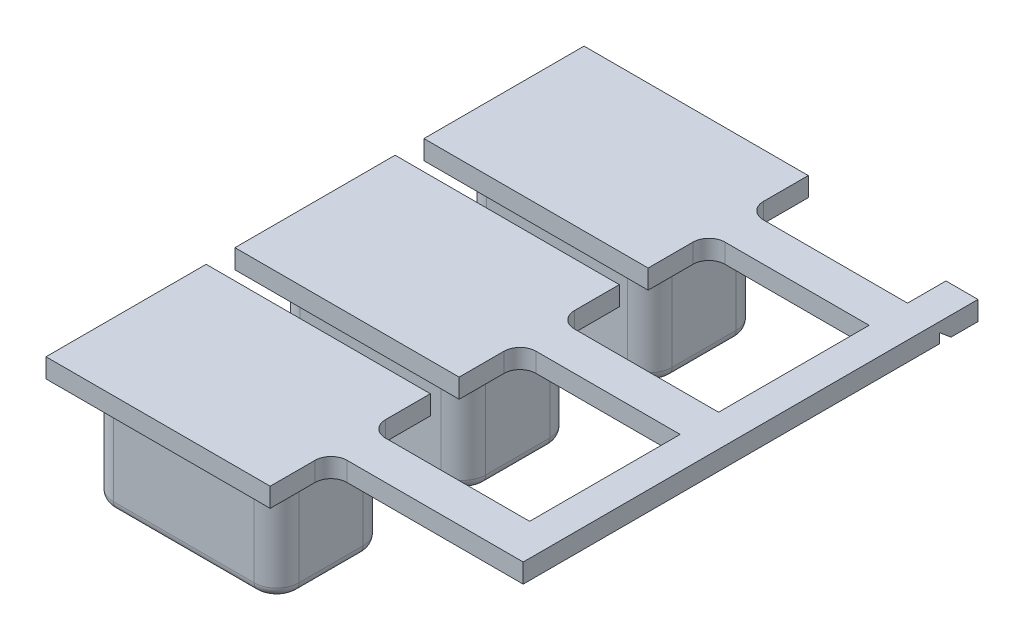
SolidWorks part; units mm, degrees
ref_plane "前视基准面" through (0, 0, 0) normal (0, 0, 1) x (1, 0, 0)
ref_plane "上视基准面" through (0, 0, 0) normal (0, 1, 0) x (1, 0, 0)
ref_plane "右视基准面" through (0, 0, 0) normal (1, 0, 0) x (0, 0, -1)
sketch "草图1" plane through (0, 0, 0) normal (0, 1, 0) x (1, 0, 0)
  line L0 (-2.2, 1.7) -> (2.2, 1.7)
  line L5 (-2.2, 7.5287) -> (2.2, 7.5287)
  line L6 (2.9, 6.8287) -> (2.9, 4.8287)
  line L7 (2.9, 1) -> (2.9, -1)
  line L8 (-2.2, -1.7) -> (2.2, -1.7)
  line L9 (-2.9, 1) -> (-2.9, -1)
  line L10 (-2.2, 4.1287) -> (2.2, 4.1287)
  line L11 (-2.9, 6.8287) -> (-2.9, 4.8287)
  line L12 (-2.2, 13.3491) -> (2.2, 13.3491)
  line L13 (2.9, 12.6491) -> (2.9, 10.6491)
  line L14 (-2.2, 9.9491) -> (2.2, 9.9491)
  line L15 (-2.9, 12.6491) -> (-2.9, 10.6491)
  arc A4 (2.2, 1.7) -> (2.9, 1) centre (2.2, 1) cw
  arc A5 (2.2, -1.7) -> (2.9, -1) centre (2.2, -1) ccw
  arc A6 (-2.9, -1) -> (-2.2, -1.7) centre (-2.2, -1) ccw
  arc A7 (-2.2, 1.7) -> (-2.9, 1) centre (-2.2, 1) ccw
  arc A8 (2.2, 7.5287) -> (2.9, 6.8287) centre (2.2, 6.8287) cw
  arc A9 (2.2, 4.1287) -> (2.9, 4.8287) centre (2.2, 4.8287) ccw
  arc A10 (-2.9, 4.8287) -> (-2.2, 4.1287) centre (-2.2, 4.8287) ccw
  arc A11 (-2.2, 7.5287) -> (-2.9, 6.8287) centre (-2.2, 6.8287) ccw
  arc A12 (2.2, 13.3491) -> (2.9, 12.6491) centre (2.2, 12.6491) cw
  arc A13 (2.2, 9.9491) -> (2.9, 10.6491) centre (2.2, 10.6491) ccw
  arc A14 (-2.9, 10.6491) -> (-2.2, 9.9491) centre (-2.2, 10.6491) ccw
  arc A15 (-2.2, 13.3491) -> (-2.9, 12.6491) centre (-2.2, 12.6491) ccw
  point P0 (0, 0)
  point P1 (-0.0497, 5.8287)
  point P15 (-0.0145, 11.6491)
  dimension "D1" = 3.4
  dimension "D2" = 5.8
extrude "凸台-拉伸1" add sketch "草图1" along normal blind 4
sketch "草图2" plane through (0, 4, 0) normal (0, 1, 0) x (1, 0, 0)
  line L1 (-3.4633, 14.2631) -> (3.5367, 14.2631)
  line L2 (-3.4633, 14.2631) -> (-3.4633, 9.2631)
  line L3 (-3.4633, 9.2631) -> (3.5367, 9.2631)
  line L4 (3.5367, 14.2631) -> (3.5367, 9.2631)
  line L5 (-3.4633, 8.3631) -> (3.5367, 8.3631)
  line L6 (-3.4633, 8.3631) -> (-3.4633, 3.3631)
  line L7 (-3.4633, 3.3631) -> (3.5367, 3.3631)
  line L8 (3.5367, 8.3631) -> (3.5367, 3.3631)
  line L9 (3.5367, 2.4631) -> (-3.4633, 2.4631)
  line L10 (3.5367, 2.4631) -> (3.5367, -2.5369)
  line L11 (3.5367, -2.5369) -> (-3.4633, -2.5369)
  line L12 (-3.4633, 2.4631) -> (-3.4633, -2.5369)
  dimension "D1" = 5
  dimension "D2" = 5
  dimension "D3" = 5
  dimension "D4" = 7
  dimension "D5" = 0.9
  dimension "D6" = 0.9
extrude "凸台-拉伸2" add sketch "草图2" against normal blind 0.6
sketch "草图3" plane through (0, 4, 0) normal (0, 1, 0) x (1, 0, 0)
  line L0 (3.5367, 9.2631) -> (3.5367, 14.2631) construction
  line L1 (3.5367, 12.3631) -> (9.5367, 12.3631)
  line L2 (3.5367, 12.3631) -> (3.5367, 11.1631)
  line L3 (3.5367, 11.1631) -> (9.5367, 11.1631)
  line L4 (9.5367, 12.3631) -> (9.5367, 11.1631)
  line L5 (3.5367, 3.3631) -> (3.5367, 8.3631) construction
  line L6 (3.5367, 6.4631) -> (9.5367, 6.4631)
  line L7 (3.5367, 6.4631) -> (3.5367, 5.2631)
  line L8 (3.5367, 5.2631) -> (9.5367, 5.2631)
  line L9 (9.5367, 6.4631) -> (9.5367, 5.2631)
  line L10 (3.5367, -2.5369) -> (3.5367, 2.4631) construction
  line L11 (3.5367, 0.5631) -> (9.5367, 0.5631)
  line L12 (3.5367, 0.5631) -> (3.5367, -0.6369)
  line L13 (3.5367, -0.6369) -> (9.5367, -0.6369)
  line L14 (9.5367, 0.5631) -> (9.5367, -0.6369)
  line L15 (-3.4633, 14.2631) -> (-3.4633, 9.2631) construction
  line L16 (-3.4633, 8.3631) -> (-3.4633, 3.3631) construction
  line L17 (-3.4633, 2.4631) -> (-3.4633, -2.5369) construction
  point P20 (-3.4633, 11.7631)
  point P21 (9.5367, 11.7631)
  point P24 (-3.4633, 5.8631)
  point P25 (9.5367, 5.8631)
  point P28 (-3.4633, -0.0369)
  point P29 (9.5367, -0.0369)
  dimension "D3" = 1.2
  dimension "D4" = 6
extrude "凸台-拉伸3" add sketch "草图3" against normal blind 0.6
sketch "草图4" plane through (0, 3.4, 0) normal (0, -1, 0) x (1, 0, 0)
  line L0 (3.5367, 0.6369) -> (9.5367, 0.6369) construction
  line L1 (9.5367, 0.6369) -> (8.5367, 0.6369)
  line L2 (9.5367, 0.6369) -> (9.5367, -12.3631)
  line L3 (9.5367, -12.3631) -> (8.5367, -12.3631)
  line L4 (8.5367, 0.6369) -> (8.5367, -12.3631)
  line L5 (9.5367, -12.3631) -> (3.5367, -12.3631) construction
  dimension "D1" = 1
extrude "凸台-拉伸4" add sketch "草图4" against normal blind 0.6
fillet "圆角1" radius 0.5 6 edges at (3.5367, 3.7, -12.3631) (3.5367, 3.7, -11.1631) (3.5367, 3.7, -5.2631) (3.5367, 3.7, -6.4631) (3.5367, 3.7, 0.6369) (3.5367, 3.7, -0.5631)
sketch "草图5" plane through (0, 0, -12.3631) normal (0, 0, -1) x (-1, 0, 0)
  line L0 (-4.0367, 4) -> (-9.5367, 4) construction
  line L1 (-9.5367, 3.4) -> (-8.5367, 3.4)
  line L2 (-9.5367, 3.4) -> (-9.5367, 4)
  line L3 (-9.5367, 4) -> (-8.5367, 4)
  line L4 (-8.5367, 3.4) -> (-8.5367, 4)
  dimension "D1" = 1
  dimension "D2" = 0.6
extrude "凸台-拉伸5" add sketch "草图5" along normal blind 1.2
sketch "草图6" plane through (8.5367, 0, 0) normal (-1, 0, 0) x (0, 0, 1)
  line L0 (-12.3631, 3.4) -> (-12.3631, 3.7)
  line L1 (-12.3631, 3.4) -> (-12.3631, 4) construction
  line L2 (-12.3631, 3.7) -> (-12.7202, 3.4)
  line L3 (-13.5631, 3.4) -> (-12.3631, 3.4) construction
  line L4 (-12.7202, 3.4) -> (-12.3631, 3.4)
extrude "切除-拉伸1" cut sketch "草图6" against normal blind 1
fillet "圆角2" radius 0.3 24 edges at (2.695, 0, -13.1441) (2.9, 0, -11.6491) (2.695, 0, -10.1542) (0, 0, -9.9491) (-2.695, 0, -10.1542) (-2.9, 0, -11.6491) (-2.695, 0, -13.1441) (2.695, 0, -7.3237) (2.9, 0, -5.8287) (2.695, 0, -4.3337) (0, 0, -4.1287) (-2.695, 0, -4.3337) (-2.9, 0, -5.8287) (-2.695, 0, -7.3237) (2.695, 0, -1.495) (2.9, 0, 0) (2.695, 0, 1.495) (0, 0, 1.7) (-2.695, 0, 1.495) (-2.9, 0, 0) (-2.695, 0, -1.495) (0, 0, -13.3491) (0, 0, -7.5287) (0, 0, -1.7)
